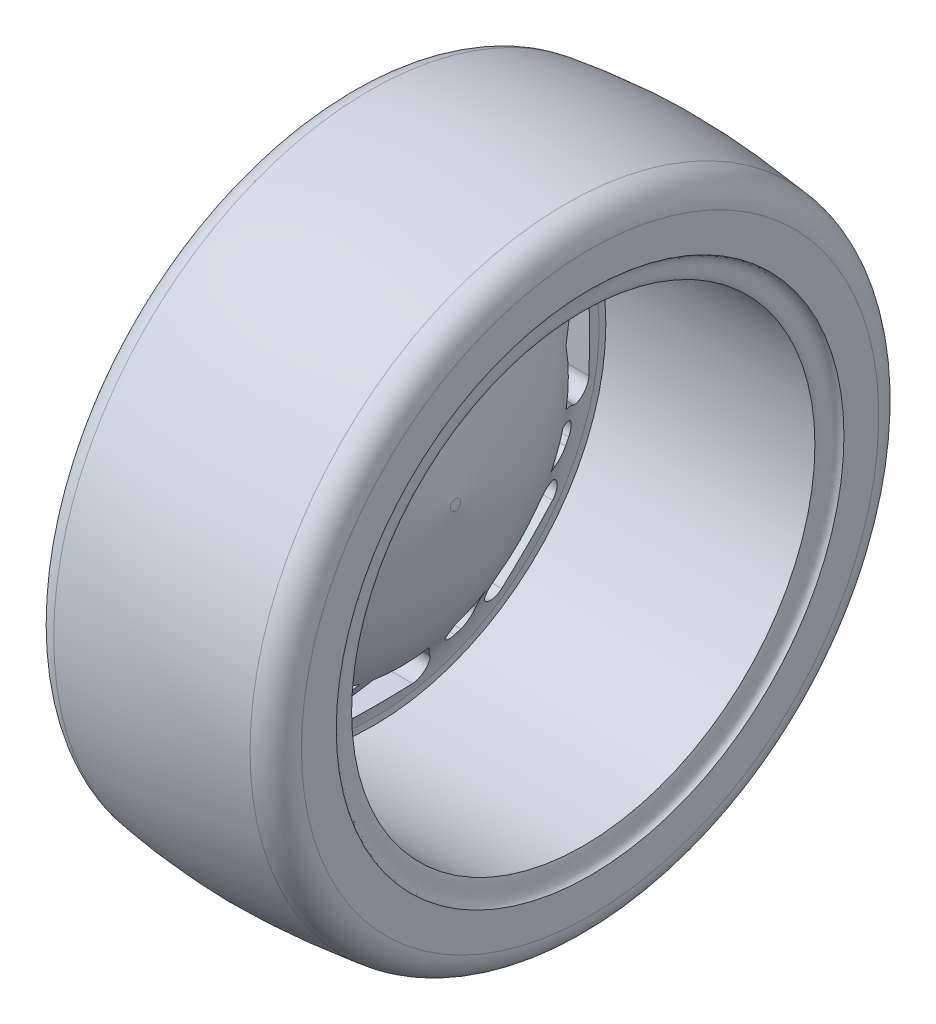
SolidWorks part; units mm, degrees
ref_plane "Front Plane" through (0, 0, 0) normal (0, 0, 1) x (1, 0, 0)
ref_plane "Top Plane" through (0, 0, 0) normal (0, 1, 0) x (1, 0, 0)
ref_plane "Right Plane" through (0, 0, 0) normal (1, 0, 0) x (0, 0, -1)
sketch "Sketch1" plane through (0, 0, 0) normal (0, 0, 1) x (1, 0, 0)
  line L0 (0, 0) -> (0, -99.3115) construction
  line L2 (-44.3922, 6.203) -> (-44.3922, -11.1159)
  line L3 (-34.1814, -14.6722) -> (42.1899, -14.6722)
  line L4 (44.697, 6.1592) -> (44.697, -6.5678)
  line L5 (-44.697, 14.6722) -> (44.697, -14.6722) construction
  line L6 (-40.2471, -13.3022) -> (44.3922, 14.6722) construction
  line L7 (-4.469, -99.3115) -> (-14.2863, -99.3115)
  line L8 (-44.3922, -11.1159) -> (-44.1265, -18.2285)
  line L13 (-4.469, -97.4088) -> (-4.469, -99.3115)
  line L14 (-34.1814, -17.182) -> (-34.1814, -14.6722)
  line L15 (42.1899, -14.6722) -> (-25.2592, -14.6722)
  line L16 (-14.2863, -99.3115) -> (0, -99.3115) construction
  arc A0 (44.697, 6.1592) -> (35.8627, 16.091) centre (34.697, 6.1592) ccw
  arc A1 (-44.3922, 6.203) -> (-35.8647, 16.094) centre (-34.3922, 6.203) cw
  arc A2 (-25.2592, -14.6722) -> (-32.09, -25.5405) centre (-25.2592, -22.2529) ccw
  spline S0 degree 3 poles (-35.8647, 16.094) (-23.9373, 17.8698) (0.0359, 19.8291) (23.8631, 17.4993) (35.8627, 16.091) knots 0.096298 0.096298 0.096298 0.096298 0.500124 0.90393 0.90393 0.90393 0.90393
  spline S1 degree 3 poles (-44.1265, -18.2285) (-43.5278, -23.9185) (-35.3247, -46.4387) (-24.7718, -45.2084) (-14.2863, -99.3115) knots 0.038573 0.038573 0.038573 0.038573 0.225612 1 1 1 1
  spline S2 degree 3 poles (44.697, -6.5678) (41.4021, -8.0833) (43.246, -12.2752) (42.1899, -14.6722) knots 0 0 0 0 1 1 1 1
  spline S3 degree 1 poles (-34.1814, -17.182) (-4.469, -97.4088) knots 0 0 1 1 construction
  spline S4 degree 3 poles (-34.1814, -17.182) (-34.1451, -17.5265) (-34.0604, -18.2247) (-33.859, -19.532) (-33.5473, -21.066) (-33.0954, -22.7526) (-32.6486, -24.1031) (-32.2565, -25.1376) (-31.8663, -26.087) (-31.1665, -27.6389) (-30.1043, -29.6619) (-28.7375, -31.8744) (-26.6336, -34.9534) (-23.9665, -38.6798) (-20.9823, -43.6005) (-18.6857, -47.9724) (-16.371, -53.1459) (-14.0488, -59.2706) (-12.1004, -65.3172) (-10.5273, -70.8186) (-9.3388, -75.3022) (-8.1402, -80.1689) (-7.1317, -84.566) (-6.319, -88.2998) (-5.7054, -91.2159) (-5.0912, -94.2328) (-4.6725, -96.3591) (-4.469, -97.4088) knots 0.038573 0.038573 0.038573 0.038573 0.053595 0.068617 0.098662 0.128707 0.158751 0.176799 0.191822 0.21884 0.27893 0.339019 0.399108 0.519286 0.579376 0.639465 0.699554 0.759643 0.819732 0.849777 0.879822 0.909866 0.939911 0.954933 0.969955 0.984978 1 1 1 1
  point P0 (0, 0)
  dimension "D2" = 10
  dimension "D1" = 10
revolve "Revolve6" add sketch "Sketch1" angle 360 about L16
sketch "Sketch2" plane through (-44.3922, 0, 0) normal (-1, 0, 0) x (0, 0, 1)
  line L0 (46.072, -35.1648) -> (64.689, -53.7818)
  line L1 (61.831, -62.2712) -> (46.1598, -64.4145)
  line L2 (-16.8805, -29.2372) -> (-8.1996, -41.6722)
  line L3 (17.5297, -29.3989) -> (7.964, -41.9957)
  line L4 (-12.7807, -21.3751) -> (13.5477, -21.3751)
  line L5 (37.6137, -37.8251) -> (34.9591, -52.7563)
  line L6 (77.9364, -86.5308) -> (77.9364, -112.8592)
  line L7 (69.9126, -116.8412) -> (57.3158, -107.2755)
  line L8 (70.0743, -82.431) -> (57.6393, -91.1118)
  line L9 (64.1467, -145.3835) -> (45.5297, -164.0005)
  line L10 (37.0403, -161.1425) -> (34.897, -145.4713)
  line L11 (61.4864, -136.9252) -> (46.5552, -134.2706)
  line L12 (12.7807, -177.2479) -> (-13.5477, -177.2479)
  line L13 (-17.5297, -169.2241) -> (-7.964, -156.6273)
  line L14 (16.8805, -169.3858) -> (8.1996, -156.9508)
  line L15 (-46.072, -163.4582) -> (-64.689, -144.8412)
  line L16 (-61.831, -136.3518) -> (-46.1598, -134.2084)
  line L17 (-37.6137, -160.7979) -> (-34.9591, -145.8666)
  line L18 (-77.9364, -112.0922) -> (-77.9364, -85.7638)
  line L19 (-69.9126, -81.7818) -> (-57.3158, -91.3475)
  line L20 (-70.0743, -116.192) -> (-57.6393, -107.5111)
  line L21 (-64.1467, -53.2394) -> (-45.5297, -34.6225)
  line L22 (-37.0403, -37.4805) -> (-34.897, -53.1517)
  line L23 (-61.4864, -61.6978) -> (-46.5552, -64.3524)
  line L24 (0, -97.4088) -> (0, -17.182) construction
  circle A0 centre (0, -99.3115) radius 81.083 construction
  arc A1 (7.964, -41.9957) -> (-8.1996, -41.6722) centre (0, -35.948) cw
  arc A2 (-12.7807, -21.3751) -> (-16.8805, -29.2372) centre (-12.7807, -26.3751) ccw
  arc A3 (17.5297, -29.3989) -> (13.5477, -21.3751) centre (13.5477, -26.3751) ccw
  arc A4 (61.831, -62.2712) -> (64.689, -53.7818) centre (61.1535, -57.3173) ccw
  arc A5 (46.072, -35.1648) -> (37.6137, -37.8251) centre (42.5365, -38.7003) ccw
  arc A6 (46.1598, -64.4145) -> (34.9591, -52.7563) centre (44.8047, -54.5068) cw
  arc A7 (69.9126, -116.8412) -> (77.9364, -112.8592) centre (72.9364, -112.8592) ccw
  arc A8 (77.9364, -86.5308) -> (70.0743, -82.431) centre (72.9364, -86.5308) ccw
  arc A9 (57.3158, -107.2755) -> (57.6393, -91.1118) centre (63.3635, -99.3115) cw
  arc A10 (37.0403, -161.1425) -> (45.5297, -164.0005) centre (41.9942, -160.465) ccw
  arc A11 (64.1467, -145.3835) -> (61.4864, -136.9252) centre (60.6112, -141.848) ccw
  arc A12 (34.897, -145.4713) -> (46.5552, -134.2706) centre (44.8047, -144.1162) cw
  arc A13 (-17.5297, -169.2241) -> (-13.5477, -177.2479) centre (-13.5477, -172.2479) ccw
  arc A14 (12.7807, -177.2479) -> (16.8805, -169.3858) centre (12.7807, -172.2479) ccw
  arc A15 (-7.964, -156.6273) -> (8.1996, -156.9508) centre (0, -162.6749) cw
  arc A16 (-61.831, -136.3518) -> (-64.689, -144.8412) centre (-61.1535, -141.3056) ccw
  arc A17 (-46.072, -163.4582) -> (-37.6137, -160.7979) centre (-42.5365, -159.9226) ccw
  arc A18 (-46.1598, -134.2084) -> (-34.9591, -145.8666) centre (-44.8047, -144.1162) cw
  arc A19 (-69.9126, -81.7818) -> (-77.9364, -85.7638) centre (-72.9364, -85.7638) ccw
  arc A20 (-77.9364, -112.0922) -> (-70.0743, -116.192) centre (-72.9364, -112.0922) ccw
  arc A21 (-57.3158, -91.3475) -> (-57.6393, -107.5111) centre (-63.3635, -99.3115) cw
  arc A22 (-37.0403, -37.4805) -> (-45.5297, -34.6225) centre (-41.9942, -38.158) ccw
  arc A23 (-64.1467, -53.2394) -> (-61.4864, -61.6978) centre (-60.6112, -56.775) ccw
  arc A24 (-34.897, -53.1517) -> (-46.5552, -64.3524) centre (-44.8047, -54.5068) cw
  point P1 (0, -49.3814)
  point P13 (-0.3399, -52.9309)
  point P15 (-22.369, -21.3751)
  point P18 (23.6228, -21.3751)
  point P80 (0, 0)
  point P81 (0, -42.9778)
  point P82 (0, -37.4805)
  dimension "D1" = 10
  dimension "D2" = 5
  dimension "D3" = 5
  dimension "D4" = 8
extrude "Cut-Extrude1" cut sketch "Sketch2" against normal blind 20
sketch "Sketch3" plane through (-44.3922, 0, 0) normal (-1, 0, 0) x (0, 0, 1)
  line L0 (-27.0156, -30.1375) -> (-29.1725, -31.4595)
  line L1 (-30.8227, -38.3353) -> (-18.9662, -57.6801)
  line L2 (-12.0903, -59.3303) -> (-9.9335, -58.0084)
  line L3 (-8.2833, -51.1326) -> (-20.1398, -31.7877)
  line L4 (28.2105, -59.3867) -> (33.5055, -37.324)
  line L5 (29.8105, -31.2952) -> (27.3506, -30.7048)
  line L6 (21.3218, -34.3999) -> (16.0267, -56.4626)
  line L7 (19.7218, -62.4914) -> (22.1817, -63.0818)
  line L8 (48.1789, -91.0282) -> (67.5238, -79.1717)
  line L9 (69.174, -72.2959) -> (67.852, -70.139)
  line L10 (60.9762, -68.4888) -> (41.6313, -80.3453)
  line L11 (39.9812, -87.2211) -> (41.3031, -89.378)
  line L12 (39.9248, -127.522) -> (61.9875, -132.817)
  line L13 (68.0163, -129.122) -> (68.6067, -126.662)
  line L14 (64.9116, -120.6332) -> (42.8489, -115.3382)
  line L15 (36.8201, -119.0333) -> (36.2297, -121.4932)
  line L16 (8.2833, -147.4904) -> (20.1398, -166.8353)
  line L17 (27.0156, -168.4855) -> (29.1725, -167.1635)
  line L18 (30.8227, -160.2877) -> (18.9662, -140.9428)
  line L19 (12.0903, -139.2926) -> (9.9335, -140.6146)
  line L20 (-28.2105, -139.2363) -> (-33.5055, -161.299)
  line L21 (-29.8105, -167.3278) -> (-27.3506, -167.9182)
  line L22 (-21.3218, -164.2231) -> (-16.0267, -142.1604)
  line L23 (-19.7218, -136.1316) -> (-22.1817, -135.5412)
  line L24 (-48.1789, -107.5948) -> (-67.5238, -119.4513)
  line L25 (-69.174, -126.3271) -> (-67.852, -128.484)
  line L26 (-60.9762, -130.1342) -> (-41.6313, -118.2776)
  line L27 (-39.9812, -111.4018) -> (-41.3031, -109.2449)
  line L28 (-39.9248, -71.101) -> (-61.9875, -65.8059)
  line L29 (-68.0163, -69.501) -> (-68.6067, -71.9609)
  line L30 (-64.9116, -77.9897) -> (-42.8489, -83.2848)
  line L31 (-36.8201, -79.5897) -> (-36.2297, -77.1298)
  arc A0 (-30.8227, -38.3353) -> (-29.1725, -31.4595) centre (-26.5597, -35.7225) cw
  arc A1 (-12.0903, -59.3303) -> (-18.9662, -57.6801) centre (-14.7032, -55.0673) cw
  arc A2 (-8.2833, -51.1326) -> (-9.9335, -58.0084) centre (-12.5463, -53.7454) cw
  arc A3 (-20.1398, -31.7877) -> (-27.0156, -30.1375) centre (-24.4028, -34.4005) ccw
  arc A4 (33.5055, -37.324) -> (29.8105, -31.2952) centre (28.6436, -36.1571) ccw
  arc A5 (28.2105, -59.3867) -> (22.1817, -63.0818) centre (23.3486, -58.2198) cw
  arc A6 (21.3218, -34.3999) -> (27.3506, -30.7048) centre (26.1837, -35.5667) cw
  arc A7 (19.7218, -62.4914) -> (16.0267, -56.4626) centre (20.8886, -57.6294) cw
  arc A8 (67.5238, -79.1717) -> (69.174, -72.2959) centre (64.911, -74.9087) ccw
  arc A9 (48.1789, -91.0282) -> (41.3031, -89.378) centre (45.5661, -86.7652) cw
  arc A10 (60.9762, -68.4888) -> (67.852, -70.139) centre (63.589, -72.7518) cw
  arc A11 (39.9812, -87.2211) -> (41.6313, -80.3453) centre (44.2442, -84.6083) cw
  arc A12 (61.9875, -132.817) -> (68.0163, -129.122) centre (63.1544, -127.9551) ccw
  arc A13 (39.9248, -127.522) -> (36.2297, -121.4932) centre (41.0917, -122.66) cw
  arc A14 (64.9116, -120.6332) -> (68.6067, -126.662) centre (63.7448, -125.4952) cw
  arc A15 (36.8201, -119.0333) -> (42.8489, -115.3382) centre (41.682, -120.2001) cw
  arc A16 (20.1398, -166.8353) -> (27.0156, -168.4855) centre (24.4028, -164.2225) ccw
  arc A17 (8.2833, -147.4904) -> (9.9335, -140.6146) centre (12.5463, -144.8776) cw
  arc A18 (30.8227, -160.2877) -> (29.1725, -167.1635) centre (26.5597, -162.9005) cw
  arc A19 (12.0903, -139.2926) -> (18.9662, -140.9428) centre (14.7032, -143.5556) cw
  arc A20 (-33.5055, -161.299) -> (-29.8105, -167.3278) centre (-28.6436, -162.4659) ccw
  arc A21 (-28.2105, -139.2363) -> (-22.1817, -135.5412) centre (-23.3486, -140.4031) cw
  arc A22 (-21.3218, -164.2231) -> (-27.3506, -167.9182) centre (-26.1837, -163.0562) cw
  arc A23 (-19.7218, -136.1316) -> (-16.0267, -142.1604) centre (-20.8886, -140.9935) cw
  arc A24 (-67.5238, -119.4513) -> (-69.174, -126.3271) centre (-64.911, -123.7143) ccw
  arc A25 (-48.1789, -107.5948) -> (-41.3031, -109.2449) centre (-45.5661, -111.8578) cw
  arc A26 (-60.9762, -130.1342) -> (-67.852, -128.484) centre (-63.589, -125.8712) cw
  arc A27 (-39.9812, -111.4018) -> (-41.6313, -118.2776) centre (-44.2442, -114.0146) cw
  arc A28 (-61.9875, -65.8059) -> (-68.0163, -69.501) centre (-63.1544, -70.6679) ccw
  arc A29 (-39.9248, -71.101) -> (-36.2297, -77.1298) centre (-41.0917, -75.9629) cw
  arc A30 (-64.9116, -77.9897) -> (-68.6067, -71.9609) centre (-63.7448, -73.1278) cw
  arc A31 (-36.8201, -79.5897) -> (-42.8489, -83.2848) centre (-41.682, -78.4228) cw
  dimension "D1" = 5
  dimension "D2" = 8
extrude "Cut-Extrude2" cut sketch "Sketch3" against normal blind 20
